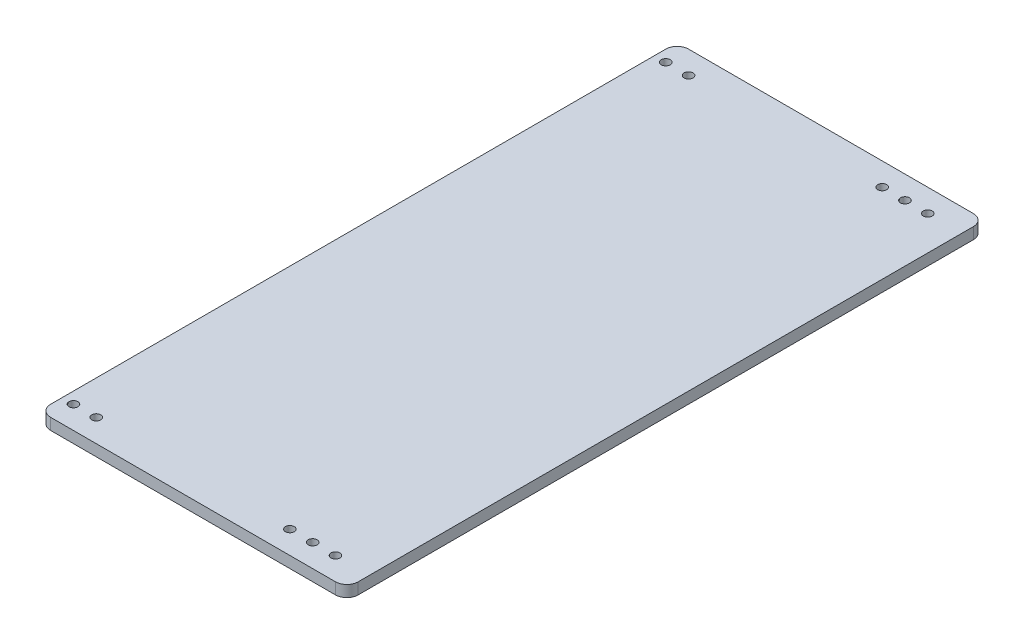
SolidWorks part; units mm, degrees
material "PC High Viscosity"
ref_plane "Front Plane" through (0, 0, 0) normal (0, 0, 1) x (1, 0, 0)
ref_plane "Top Plane" through (0, 0, 0) normal (0, 1, 0) x (1, 0, 0)
ref_plane "Right Plane" through (0, 0, 0) normal (1, 0, 0) x (0, 0, -1)
sketch "Sketch1" plane through (0, 0, 0) normal (0, 1, 0) x (1, 0, 0)
  line L1 (-85.725, -177.8) -> (85.725, -177.8)
  line L2 (-85.725, -177.8) -> (-85.725, 177.8)
  line L3 (-85.725, 177.8) -> (85.725, 177.8)
  line L4 (85.725, -177.8) -> (85.725, 177.8)
  line L5 (-85.725, -177.8) -> (85.725, 177.8) construction
  line L6 (-85.725, 177.8) -> (85.725, -177.8) construction
  point P0 (0, 0)
  dimension "D1" = 171.45
  dimension "D2" = 355.6
extrude "Boss-Extrude1" add sketch "Sketch1" along normal blind 6.35
sketch "Sketch2" plane through (0, 6.35, 0) normal (0, 1, 0) x (1, 0, 0)
  line L0 (85.725, -177.8) -> (85.725, 177.8) construction
  line L1 (-85.725, -177.8) -> (85.725, -177.8) construction
  line L2 (-85.725, 0) -> (85.725, 0) construction
  line L3 (-85.725, 177.8) -> (-85.725, -177.8) construction
  line L4 (0, 177.8) -> (0, -177.8) construction
  line L5 (85.725, 177.8) -> (-85.725, 177.8) construction
  circle A0 centre (79.375, -165.1) radius 2.4892 construction
  circle A1 centre (66.675, -165.1) radius 2.4892
  circle A2 centre (53.975, -165.1) radius 2.4892
  circle A3 centre (41.275, -165.1) radius 2.4892
  circle A4 centre (79.375, 165.1) radius 2.4892 construction
  circle A5 centre (66.675, 165.1) radius 2.4892
  circle A6 centre (53.975, 165.1) radius 2.4892
  circle A7 centre (41.275, 165.1) radius 2.4892
  circle A8 centre (79.375, 165.1) radius 2.4892 construction
  circle A9 centre (66.675, 165.1) radius 2.4892
  circle A10 centre (53.975, 165.1) radius 2.4892
  circle A11 centre (41.275, 165.1) radius 2.4892
  circle A12 centre (-79.375, -165.1) radius 2.4892
  circle A13 centre (-66.675, -165.1) radius 2.4892
  circle A14 centre (-53.975, -165.1) radius 2.4892 construction
  circle A15 centre (-41.275, -165.1) radius 2.4892 construction
  circle A16 centre (-79.375, 165.1) radius 2.4892
  circle A17 centre (-66.675, 165.1) radius 2.4892
  circle A18 centre (-53.975, 165.1) radius 2.4892 construction
  circle A19 centre (-41.275, 165.1) radius 2.4892 construction
  dimension "D1" = 4.9784
  dimension "D2" = 6.35
  dimension "D3" = 12.7
  dimension "D5" = 12.7
  dimension "D4" = 4
extrude "Cut-Extrude2" cut sketch "Sketch2" against normal through all contours A15 | A14 | A13 | A12 | A4 | A5 | A6 | A7 | A16 | A17 | A18 | A19 | A3 | A2 | A1 | A0 region at (66.675, 6.35, -165.1) region at (53.975, 6.35, -165.1) region at (41.275, 6.35, -165.1) region at (-79.375, 6.35, 165.1) region at (-66.675, 6.35, 165.1) region at (-79.375, 6.35, -165.1) region at (-66.675, 6.35, -165.1)
fillet "Fillet1" radius 6.35 4 edges at (85.725, 3.175, 177.8) (-85.725, 3.175, 177.8) (-85.725, 3.175, -177.8) (85.725, 3.175, -177.8)
